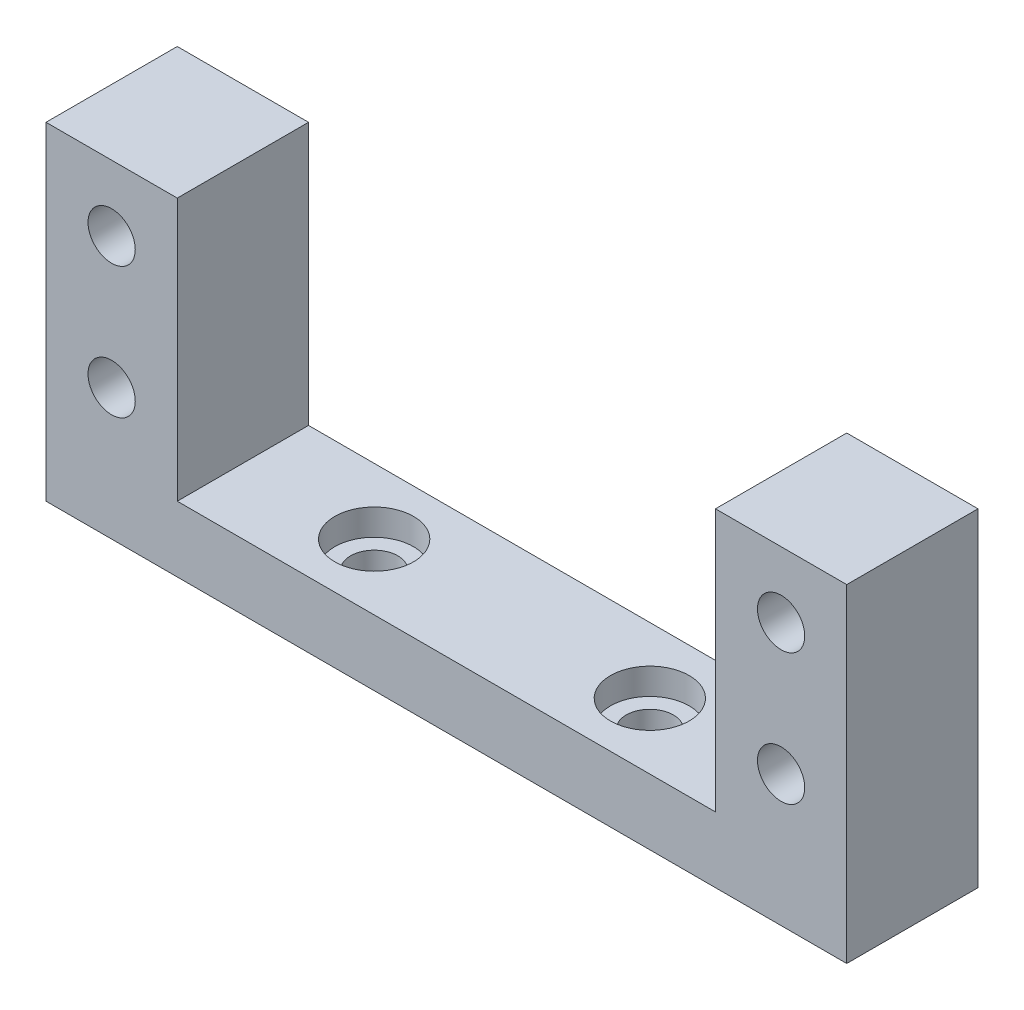
SolidWorks part; units mm, degrees
ref_plane "Plan de face" through (0, 0, 0) normal (0, 0, 1) x (1, 0, 0)
ref_plane "Plan de dessus" through (0, 0, 0) normal (0, 1, 0) x (1, 0, 0)
ref_plane "Plan de droite" through (0, 0, 0) normal (1, 0, 0) x (0, 0, -1)
sketch "Esquisse1" plane through (0, 0, 0) normal (0, 0, 1) x (1, 0, 0)
  line L0 (-10, 25) -> (0, 25)
  line L1 (-10, 25) -> (-10, 0)
  line L2 (0, 25) -> (0, 0)
  line L3 (-10, 0) -> (0, 0)
  line L4 (41, 25) -> (51, 25)
  line L5 (41, 25) -> (41, 0)
  line L6 (51, 25) -> (51, 0)
  line L7 (41, 0) -> (51, 0)
  line L8 (0, 0) -> (0, 5)
  line L9 (0, 0) -> (41, 0)
  line L10 (0, 5) -> (41, 5)
  line L11 (41, 0) -> (41, 5)
  circle A0 centre (46, 20) radius 1.8
  circle A1 centre (46, 10) radius 1.8
  circle A2 centre (-5, 20) radius 1.8
  circle A3 centre (-5, 10) radius 1.8
  dimension "D7" = 3.6
  dimension "D1" = 41
  dimension "D2" = 25
  dimension "D3" = 5
  dimension "D4" = 25
  dimension "D5" = 10
  dimension "D6" = 10
  dimension "D8" = 5
  dimension "D9" = 5
  dimension "D10" = 5
  dimension "D11" = 5
  dimension "D12" = 5
  dimension "D13" = 5
  dimension "D14" = 10
  dimension "D15" = 10
extrude "Boss.-Extru.1" add sketch "Esquisse1" along normal blind 10 contours L1 L3 L2 L0 A3 A2 | L10 L2 L9 L5 | L5 L7 L6 L4 A1 A0 region at (-5, 12.2784, 0) region at (20.5, 2.5, 0) region at (46, 12.2784, 0)
sketch "Esquisse2" plane through (0, 0, 0) normal (0, -1, 0) x (1, 0, 0)
  line L0 (41, 10) -> (41, 0) construction
  line L1 (0, 10) -> (0, 0) construction
  line L2 (-10, 0) -> (51, 0) construction
  circle A0 centre (10, 5) radius 1.8
  circle A1 centre (31, 5) radius 1.8
  dimension "D1" = 3.6
  dimension "D2" = 3.6
  dimension "D3" = 10
  dimension "D4" = 10
  dimension "D5" = 5
  dimension "D6" = 5
extrude "Enlèv. mat.-Extru.1" cut sketch "Esquisse2" against normal blind 10
sketch "Esquisse3" plane through (0, 5, 0) normal (0, 1, 0) x (1, 0, 0)
  circle A0 centre (10, -5) radius 3
  circle A1 centre (31, -5) radius 3
  dimension "D1" = 6
  dimension "D2" = 6
extrude "Enlèv. mat.-Extru.2" cut sketch "Esquisse3" against normal blind 2
